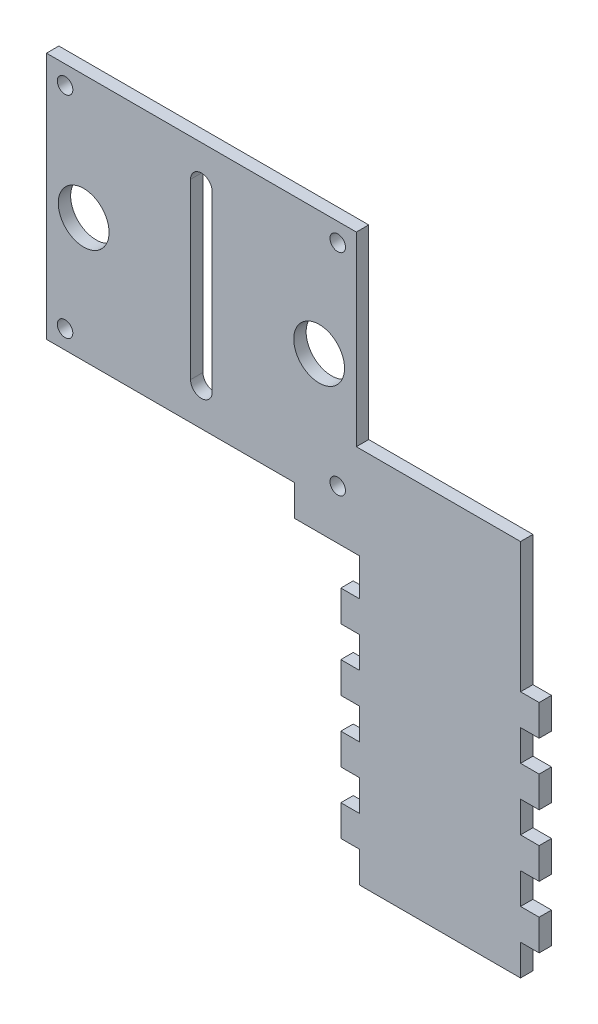
SolidWorks part; units mm, degrees
ref_plane "Front Plane" through (0, 0, 0) normal (0, 0, 1) x (1, 0, 0)
ref_plane "Top Plane" through (0, 0, 0) normal (0, 1, 0) x (1, 0, 0)
ref_plane "Right Plane" through (0, 0, 0) normal (1, 0, 0) x (0, 0, -1)
sketch "Sketch1" plane through (0, 0, 0) normal (0, 0, 1) x (1, 0, 0)
  line L1 (0, 0) -> (50, 0)
  line L2 (0, 0) -> (0, 40)
  line L3 (0, 40) -> (50, 40)
  line L4 (50, 0) -> (50, 40)
  line L5 (50, 0) -> (76.5, 0)
  line L6 (50, 0) -> (50, -51)
  line L7 (50, -51) -> (76.5, -51)
  line L8 (76.5, 0) -> (76.5, -51)
  line L9 (50, 0) -> (76.5, 0)
  line L12 (76.5, 0) -> (76.5, -21)
  line L13 (76.5, 0) -> (50, 0)
  line L14 (76.5, 0) -> (76.5, 10)
  line L15 (76.5, 10) -> (50, 10)
  line L16 (50, 0) -> (50, 10)
  line L17 (40, 0) -> (50, 0)
  line L18 (40, 0) -> (40, -5)
  line L19 (40, -5) -> (50, -5)
  line L20 (50, 0) -> (50, -5)
  dimension "D1" = 50
  dimension "D2" = 40
  dimension "D3" = 26.5
  dimension "D4" = 51
  dimension "D5" = 0
  dimension "D6" = 10
  dimension "D7" = 0
  dimension "D8" = 0
  dimension "D9" = 0
  dimension "D10" = 10
  dimension "D11" = 5
extrude "plate_body" add sketch "Sketch1" along normal blind 2 contours L1 L4 L3 L2 | L8 L5 L1 L6 L7 | L14 L15 L4 L5 | L18 L19 L6 L1 region at (25, 20, 0) region at (45, -2.5, 0) region at (63.25, 5, 0) region at (63.25, -25.5, 0)
sketch "Sketch2" plane through (0, 0, 2) normal (0, 0, 1) x (1, 0, 0)
  line L2 (0, 0) -> (0, 40) construction
  line L3 (0, 40) -> (50, 40) construction
  circle A0 centre (6, 20) radius 4.1
  circle A1 centre (44, 20) radius 4.1
  dimension "D1" = 38
  dimension "D2" = 8.2
  dimension "D3" = 8.2
  dimension "D4" = 6
  dimension "D5" = 20
  dimension "D6" = 20
extrude "shaft_bearings" cut sketch "Sketch2" against normal through all
sketch "Sketch4" plane through (0, 0, 2) normal (0, 0, 1) x (1, 0, 0)
  line L0 (25, 34) -> (25, 6) construction
  line L1 (26.75, 34) -> (26.75, 6)
  line L2 (23.25, 34) -> (23.25, 6)
  line L5 (0, 0) -> (0, 40) construction
  line L6 (0, 0) -> (40, 0) construction
  arc A0 (26.75, 34) -> (23.25, 34) centre (25, 34) ccw
  arc A1 (23.25, 6) -> (26.75, 6) centre (25, 6) ccw
  point P2 (25, 20)
  dimension "D4" = 6
  dimension "D1" = 3.5
  dimension "D2" = 28
  dimension "D3" = 25
extrude "slot" cut sketch "Sketch4" against normal through all
sketch "Sketch5" plane through (0, 0, 2) normal (0, 0, 1) x (1, 0, 0)
  line L0 (0, 40) -> (50, 40) construction
  line L1 (0, 0) -> (0, 40) construction
  line L2 (0, 0) -> (40, 0) construction
  line L3 (50, 10) -> (50, 40) construction
  circle A0 centre (3, 37) radius 1.25
  circle A1 centre (47, 37) radius 1.25
  circle A2 centre (3, 3) radius 1.25
  circle A3 centre (47, 3) radius 1.25
  dimension "D1" = 2.5
  dimension "D2" = 2.5
  dimension "D3" = 2.5
  dimension "D4" = 2.5
  dimension "D5" = 3
  dimension "D6" = 3
  dimension "D7" = 3
  dimension "D8" = 3
  dimension "D9" = 3
  dimension "D10" = 3
  dimension "D11" = 3
  dimension "D12" = 3
extrude "bolt_holes" cut sketch "Sketch5" against normal through all
sketch "Sketch6" plane through (0, 0, 2) normal (0, 0, 1) x (1, 0, 0)
  line L0 (50, -51) -> (76.5, -51) construction
  line L1 (50, -5) -> (50.5, -5)
  line L2 (50, -5) -> (50, -51)
  line L3 (50, -51) -> (50.5, -51)
  line L4 (50.5, -5) -> (50.5, -51)
  dimension "D1" = 0.5
extrude "Cut-Extrude1" cut sketch "Sketch6" against normal through all
sketch "Sketch8" plane through (0, 0, 2) normal (0, 0, 1) x (1, 0, 0)
  line L0 (50.5, -36) -> (47.5, -36)
  line L1 (50.5, -46) -> (47.5, -46)
  line L2 (50.5, -46) -> (50.5, -41)
  line L3 (50.5, -41) -> (47.5, -41)
  line L4 (47.5, -46) -> (47.5, -41)
  line L5 (76.5, -46) -> (79.5, -46)
  line L6 (76.5, -46) -> (76.5, -41)
  line L7 (76.5, -41) -> (79.5, -41)
  line L8 (79.5, -46) -> (79.5, -41)
  line L9 (50.5, -36) -> (50.5, -31)
  line L10 (50.5, -31) -> (47.5, -31)
  line L11 (47.5, -36) -> (47.5, -31)
  line L12 (76.5, -36) -> (79.5, -36)
  line L13 (76.5, -36) -> (76.5, -31)
  line L14 (76.5, -31) -> (79.5, -31)
  line L15 (79.5, -36) -> (79.5, -31)
  line L16 (50.5, -51) -> (50.5, -5) construction
  line L17 (76.5, -51) -> (76.5, 10) construction
  line L18 (50.5, -16) -> (47.5, -16)
  line L19 (50.5, -26) -> (47.5, -26)
  line L20 (50.5, -26) -> (50.5, -21)
  line L21 (50.5, -21) -> (47.5, -21)
  line L22 (47.5, -26) -> (47.5, -21)
  line L23 (76.5, -26) -> (79.5, -26)
  line L24 (76.5, -26) -> (76.5, -21)
  line L25 (76.5, -21) -> (79.5, -21)
  line L26 (79.5, -26) -> (79.5, -21)
  line L27 (50.5, -16) -> (50.5, -11)
  line L28 (50.5, -11) -> (47.5, -11)
  line L29 (47.5, -16) -> (47.5, -11)
  line L30 (76.5, -16) -> (79.5, -16)
  line L31 (76.5, -16) -> (76.5, -11)
  line L32 (76.5, -11) -> (79.5, -11)
  line L33 (79.5, -16) -> (79.5, -11)
  line L34 (50.5, -51) -> (76.5, -51) construction
  point P38 (78, -31)
  point P41 (78, -41)
  dimension "D1" = 5
  dimension "D2" = 5
  dimension "D3" = 3
  dimension "D4" = 3
  dimension "D5" = 5
  dimension "D6" = 5
  dimension "D7" = 3
  dimension "D8" = 3
  dimension "D9" = 0
  dimension "D10" = 0
  dimension "D11" = 5
  dimension "D12" = 5
  dimension "D13" = 5
  dimension "D14" = 5
  dimension "D15" = 3
  dimension "D16" = 3
  dimension "D17" = 5
  dimension "D18" = 5
  dimension "D19" = 3
  dimension "D20" = 3
  dimension "D21" = 5
  dimension "D22" = 5
  dimension "D23" = 26
  dimension "D24" = 26
  dimension "D25" = 0
  dimension "D26" = 0
  dimension "D27" = 5
  dimension "D28" = 5
  dimension "D29" = 10
  dimension "D30" = 10
extrude "finger_joints" add sketch "Sketch8" along direction (0, 0, 1) on the side against the normal up to surface (2 mm away) up to face at (48.25, 37, 0)
